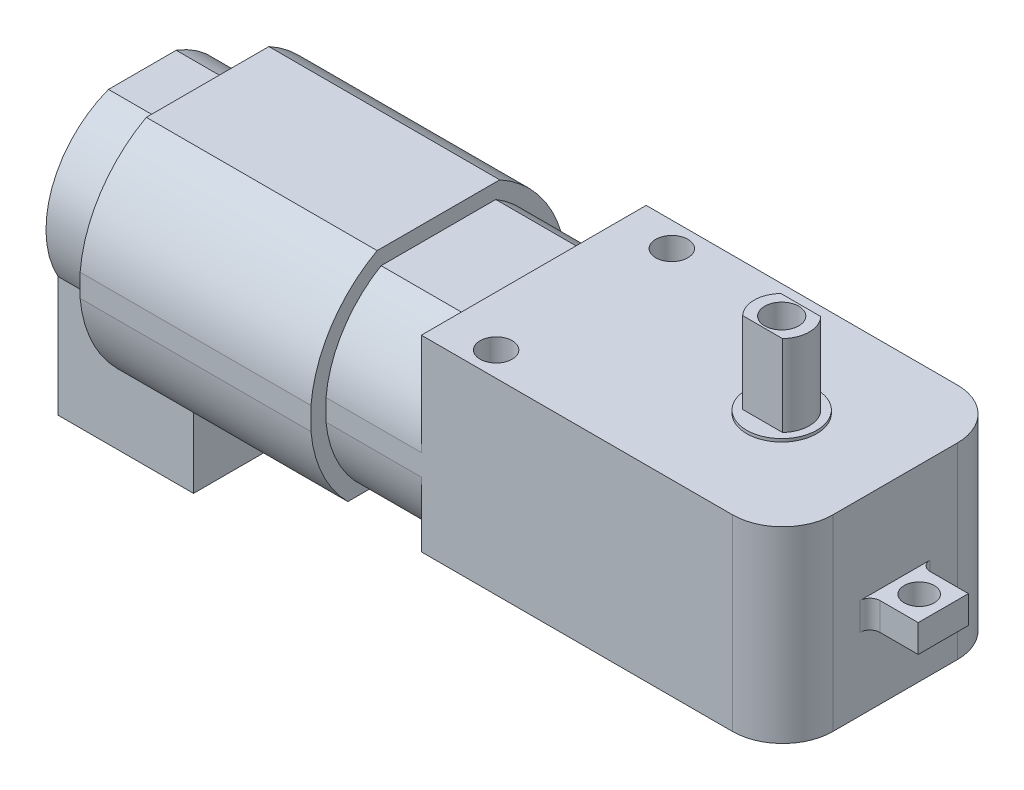
SolidWorks part; units mm, degrees
ref_plane "Front Plane" through (0, 0, 0) normal (0, 0, 1) x (1, 0, 0)
ref_plane "Top Plane" through (0, 0, 0) normal (0, 1, 0) x (1, 0, 0)
ref_plane "Right Plane" through (0, 0, 0) normal (1, 0, 0) x (0, 0, -1)
sketch "Sketch1" plane through (0, 0, 0) normal (0, 1, 0) x (1, 0, 0)
  line L0 (-13, -8.75) -> (-13, 8.75) construction
  line L1 (-18, -11.2) -> (18, -11.2)
  line L2 (-18, -11.2) -> (-18, 11.2)
  line L3 (-18, 11.2) -> (18, 11.2)
  line L4 (18, -11.2) -> (18, 11.2)
  line L5 (-18, -11.2) -> (18, 11.2) construction
  line L6 (-18, 11.2) -> (18, -11.2) construction
  circle A0 centre (-13, 8.75) radius 1.6
  circle A1 centre (-13, -8.75) radius 1.6
  point P0 (0, 0)
  point P8 (-13, 8.75)
  point P9 (-13, 0)
  dimension "D3" = 3.2
  dimension "D1" = 36
  dimension "D2" = 22.4
  dimension "D4" = 31
  dimension "D5" = 8.75
extrude "Boss-Extrude1" add sketch "Sketch1" along normal mid plane 18.7
fillet "Fillet1" radius 5 2 edges at (18, 0, 11.2) (18, 0, -11.2)
sketch "Sketch2" plane through (0, 9.35, 0) normal (0, 1, 0) x (1, 0, 0)
  line L0 (18, 0) -> (6.7, 0) construction
  line L1 (18, -6.2) -> (18, 6.2) construction
  circle A0 centre (6.7, 0) radius 3.5
  point P6 (10.2, 0)
  point P7 (0, 0)
  dimension "D1" = 7
  dimension "D2" = 7.8
extrude "Boss-Extrude2" add sketch "Sketch2" along normal blind 0.3
sketch "Sketch3" plane through (0, 9.65, 0) normal (0, 1, 0) x (1, 0, 0)
  line L0 (3.95, 0) -> (9.45, 0) construction
  line L1 (3.95, 1.905) -> (9.45, 1.905)
  line L2 (3.95, -1.905) -> (9.45, -1.905)
  circle A0 centre (6.7, 0) radius 2.75
  arc A1 (3.95, 1.905) -> (3.95, -1.905) centre (3.95, 0) ccw
  arc A2 (9.45, -1.905) -> (9.45, 1.905) centre (9.45, 0) ccw
  point P5 (6.7, 0)
  dimension "D1" = 5.5
  dimension "D2" = 3.81
extrude "Boss-Extrude4" add sketch "Sketch3" along normal offset from surface (8.4 mm away) 8.4 from surface contours A0 L0 L1 | L0 A0 L2 region at (6.7, 9.65, -0.9057) region at (6.7, 9.65, 0.9057) up to face at (6.7, 9.35, -3.5) offset beyond the face yes starting at face at (6.7, 9.35, -3.5)
sketch "Sketch4" plane through (0, 17.75, 0) normal (0, 1, 0) x (1, 0, 0)
  point P0 (6.7, 0)
hole_wizard "M3 Clearance Hole1" positions "3DSketch1" profile "Sketch6" hole size "M3" standard "ANSI Metric"
sketch3d "3DSketch1"
  point P0 (6.7, 17.75, 0)
sketch "Sketch6" plane through (6.7, 17.75, 0) normal (1, 0, 0) x (0, 0, 1)
  line L0 (0, 0) -> (0, 9.0215)
  line L1 (0, 9.0215) -> (1.7, 8)
  line L2 (1.7, 8) -> (1.7, 0)
  line L5 (1.7, 0) -> (0, 0)
  line L10 (0, 9.0215) -> (-1.7, 8) construction
  line L11 (0, -6.35) -> (0, 107.95) construction
  dimension "Hole Dia." = 3.4
  dimension "Hole Depth" = 8
  dimension "Drill Angle" = 118
sketch "Sketch7" plane through (-18, 0, 0) normal (-1, 0, 0) x (0, 0, 1)
  line L0 (11.2, 9.35) -> (11.2, -9.35) construction
  line L1 (-11.2, -9.35) -> (11.2, -9.35)
  line L2 (-11.2, -9.35) -> (-11.2, 7.85)
  line L3 (-11.2, 7.85) -> (11.2, 7.85)
  line L4 (11.2, -9.35) -> (11.2, 7.85)
  circle A0 centre (0, -1.8422) radius 11.25
  dimension "D2" = 22.5
  dimension "D1" = 17.2
extrude "Boss-Extrude5" add sketch "Sketch7" along normal blind 9.5 contours L4 A0 L3 L2 L1 region at (-18, -1.059, 0)
sketch "Sketch8" plane through (-27.5, 0, 0) normal (-1, 0, 0) x (0, 0, 1)
  line L8 (12.7, -2.9702) -> (12.7, -0.7141)
  line L9 (6.1072, 9.35) -> (-6.1072, 9.35)
  line L10 (-12.7, -0.7141) -> (-12.7, -2.9702)
  line L11 (-9.0234, -10.85) -> (9.0234, -10.85)
  line L12 (12.7, -2.9702) -> (12.7, -0.7141)
  line L13 (6.1072, 9.35) -> (-6.1072, 9.35)
  line L14 (-12.7, -0.7141) -> (-12.7, -2.9702)
  line L15 (-9.0234, -10.85) -> (9.0234, -10.85)
  arc A8 (12.7, -0.7141) -> (6.1072, 9.35) centre (0, -1.8422) ccw
  arc A9 (-6.1072, 9.35) -> (-12.7, -0.7141) centre (0, -1.8422) ccw
  arc A10 (-12.7, -2.9702) -> (-9.0234, -10.85) centre (0, -1.8422) ccw
  arc A11 (9.0234, -10.85) -> (12.7, -2.9702) centre (0, -1.8422) ccw
  arc A12 (12.7, -0.7141) -> (6.1072, 9.35) centre (0, -1.8422) ccw
  arc A13 (-6.1072, 9.35) -> (-12.7, -0.7141) centre (0, -1.8422) ccw
  arc A14 (-12.7, -2.9702) -> (-9.0234, -10.85) centre (0, -1.8422) ccw
  arc A15 (9.0234, -10.85) -> (12.7, -2.9702) centre (0, -1.8422) ccw
  dimension "D1" = 1.5
extrude "Boss-Extrude6" add sketch "Sketch8" along normal offset from surface (23 mm away) 68.5 up to face at (18, 0, 0)
ref_plane "Plane1" through (-57, 0, 0) normal (1, 0, 0) x (0, 0, -1)
sketch "Sketch9" plane through (-57, 0, 0) normal (-1, 0, 0) x (0, 0, 1)
  line L0 (-3.375, 7.145) -> (3.375, 7.145)
  line L1 (-8.4, -1.8422) -> (8.4, -1.8422)
  line L2 (-8.4, -1.8422) -> (-8.4, -18.455)
  line L3 (-8.4, -18.455) -> (8.4, -18.455)
  line L4 (8.4, -1.8422) -> (8.4, -18.455)
  circle A0 centre (0, -1.8422) radius 9.6
  point P7 (0, -1.8422)
  dimension "D2" = 19.2
  dimension "D1" = 6.75
  dimension "D3" = 25.6
  dimension "D4" = 16.8
extrude "Boss-Extrude7" add sketch "Sketch9" against normal blind 13.5 contours A0 L2 L1 L4 | L2 A0 L4 L3 | A0 L4 L1 L2 L0 region at (-57, 1.8425, 0) region at (-57, -14.1194, 0) region at (-57, -6.0437, 0)
sketch "Sketch11" plane through (0, -18.455, 0) normal (0, -1, 0) x (1, 0, 0)
  line L0 (-43.5, 8.4) -> (-43.5, -8.4) construction
  line L1 (-46.5, 6.7) -> (-50.4, 6.7)
  line L2 (-46.5, 6.7) -> (-46.5, -6.7)
  line L3 (-46.5, -6.7) -> (-50.4, -6.7)
  line L4 (-50.4, 6.7) -> (-50.4, -6.7)
  point P6 (-46.5, 0)
  dimension "D1" = 3
  dimension "D2" = 13.4
  dimension "D3" = 3.9
extrude "Cut-Extrude1" cut sketch "Sketch11" against normal blind 5
ref_plane "Plane2" through (0, -2.15, 0) normal (0, -1, 0) x (-1, 0, 0)
sketch "Sketch13" plane through (0, -2.15, 0) normal (0, 1, 0) x (1, 0, 0)
  line L0 (18, -6.2) -> (18, 6.2) construction
  line L1 (22.8, 2.5) -> (18, 2.5)
  line L2 (22.8, 2.5) -> (22.8, -2.5)
  line L3 (22.8, -2.5) -> (18, -2.5)
  line L4 (18, 2.5) -> (18, -2.5)
  line L5 (22.8, 2.5) -> (18, -2.5) construction
  line L6 (22.8, -2.5) -> (18, 2.5) construction
  circle A0 centre (20.4, 0) radius 1.5
  point P8 (0, 0)
  dimension "D3" = 3
  dimension "D1" = 5
  dimension "D2" = 4.8
extrude "Boss-Extrude8" add sketch "Sketch13" along normal blind 2.75
fillet "Fillet2" radius 1 2 edges at (18, -0.775, -2.5) (18, -0.775, 2.5)
ref_axis "Axis1" through (6.7, 17.75, 0) along (0, -1, 0)
